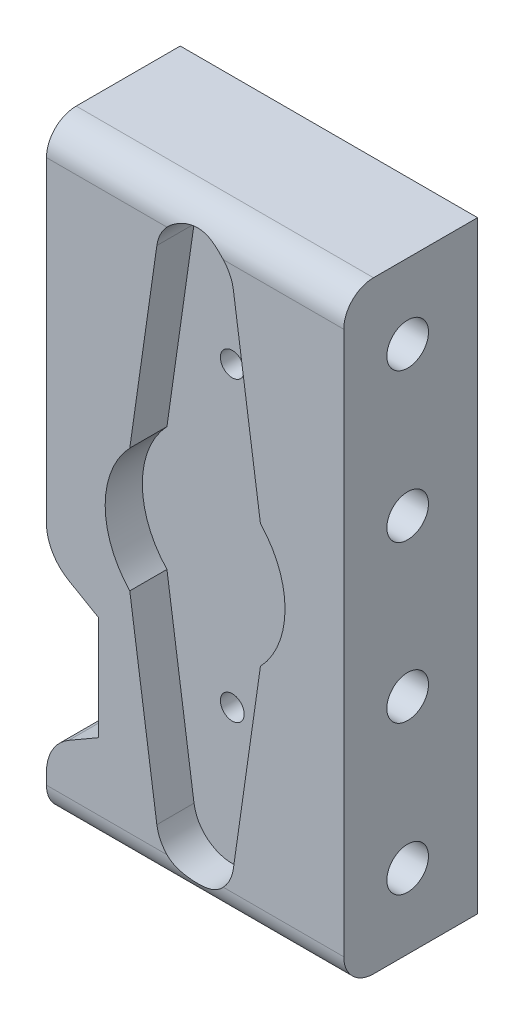
SolidWorks part; units mm, degrees
material "PLA_Holder_Servo"
ref_plane "Front Plane" through (0, 0, 0) normal (0, 0, 1) x (1, 0, 0)
ref_plane "Top Plane" through (0, 0, 0) normal (0, 1, 0) x (1, 0, 0)
ref_plane "Right Plane" through (0, 0, 0) normal (1, 0, 0) x (0, 0, -1)
sketch "Sketch1" plane through (0, 0, 0) normal (0, 0, 1) x (1, 0, 0)
  line L0 (-10, 20.2804) -> (-10, -20.2804)
  line L1 (-10, -20.2804) -> (10, -20.2804)
  line L2 (10, -20.2804) -> (10, 20.2804)
  line L3 (10, 20.2804) -> (-10, 20.2804)
  line L4 (10, -20.2804) -> (-10, 20.2804) construction
  line L5 (10, 20.2804) -> (-10, -20.2804) construction
  point P4 (0, 0)
  dimension "D1" = 20
  dimension "D2" = 40.5608
extrude "Boss-Extrude1" add sketch "Sketch1" against normal blind 9
sketch "Sketch6" plane through (10, 0, 0) normal (1, 0, 0) x (0, 0, -1)
  line L0 (0, -20.2804) -> (0, 20.2804) construction
  line L2 (4.3, 4.95) -> (4.3, 15.6283) construction
  line L3 (0, 0) -> (9, 0) construction
  line L4 (9, -20.2804) -> (9, 20.2804) construction
  line L5 (4.3, -15.2652) -> (4.3, -5.2652) construction
  line L6 (-4.0611, -10.2652) -> (12.6611, -10.2652) construction
  line L7 (9, -20.2804) -> (0, -20.2804) construction
  line L8 (-4.0611, -0.25) -> (12.6611, -0.25) construction
  circle A0 centre (4.3, -15.2652) radius 1.4
  circle A1 centre (4.3, -5.2652) radius 1.4
  circle A2 centre (4.3, 15.2652) radius 1.4
  circle A3 centre (4.3, 5.2652) radius 1.4
  point P18 (4.3, -10.2652)
  point P22 (4.3, -10.2652)
  dimension "D1" = 2.8
  dimension "D2" = 4.7
  dimension "D3" = 10.0152
  dimension "D4" = 10
  dimension "D5" = 10.0152
extrude "Cut-Extrude1" cut sketch "Sketch6" against normal blind 10
sketch "Sketch8" plane through (0, 0, 0) normal (0, 0, 1) x (1, 0, 0)
  line L0 (-10, 20.2804) -> (10, -20.2804) construction
  line L1 (-4.3945, -4.1583) -> (-2.5737, -16.8687)
  line L2 (4.3, 4.1125) -> (4.3, -4.1125) construction
  line L3 (0, -16.5) -> (0, 16.5) construction
  line L4 (2.5737, -16.8687) -> (4.3945, -4.1583)
  line L5 (-4.3, 4.1125) -> (4.3, 4.1125) construction
  line L6 (-4.3, -4.1125) -> (4.3, -4.1125) construction
  line L7 (4.3945, 4.1583) -> (2.5737, 16.8687)
  line L8 (-2.5737, 16.8687) -> (-4.3945, 4.1583)
  line L12 (-4.3, -4.1125) -> (-2.4747, -16.8545) construction
  line L13 (2.4747, -16.8545) -> (4.3, -4.1125) construction
  line L14 (4.3, 4.1125) -> (2.4747, 16.8545) construction
  line L15 (-2.4747, 16.8545) -> (-4.3, 4.1125) construction
  arc A0 (-2.5737, -16.8687) -> (2.5737, -16.8687) centre (0, -16.5) ccw
  arc A1 (4.3945, -4.1583) -> (4.3945, 4.1583) centre (0, 0) ccw
  arc A2 (2.5737, 16.8687) -> (-2.5737, 16.8687) centre (0, 16.5) ccw
  arc A3 (-4.3945, 4.1583) -> (-4.3945, -4.1583) centre (0, 0) ccw
  arc A12 (-4.3, 4.1125) -> (-4.3, -4.1125) centre (0, 0) ccw construction
  arc A13 (-2.4747, -16.8545) -> (2.4747, -16.8545) centre (0, -16.5) ccw construction
  arc A14 (4.3, -4.1125) -> (4.3, 4.1125) centre (0, 0) ccw construction
  arc A15 (2.4747, 16.8545) -> (-2.4747, 16.8545) centre (0, 16.5) ccw construction
  point P10 (0, 0)
  dimension "D1" = 5.95
  dimension "D3" = 2.5
  dimension "D2" = 8.6
  dimension "D4" = 33
  dimension "D5" = 8.225
  dimension "D6" = 0.1
extrude "Cut-Extrude2" cut sketch "Sketch8" against normal blind 2.5
fillet "Fillet1" radius 2 2 edges at (0, -20.2804, 0) (0, 20.2804, 0) tangent propagation no
sketch "Sketch9" plane through (0, 0, -2.5) normal (0, 0, 1) x (1, 0, 0)
  line L0 (0, 20) -> (0, -49980) construction
  line L1 (-6.05, 0) -> (6.05, 0) construction
  circle A0 centre (0, 10) radius 0.8
  arc A2 (-4.3945, 4.1583) -> (-4.3945, -4.1583) centre (0, 0) ccw construction
  arc A3 (4.3945, -4.1583) -> (4.3945, 4.1583) centre (0, 0) ccw construction
  circle A4 centre (0, -10) radius 0.8
  dimension "D1" = 1.6
  dimension "D2" = 10
extrude "Cut-Extrude3" cut sketch "Sketch9" against normal up to surface (6.5 mm away) up to face at (0, 0, -9)
sketch "Sketch10" plane through (-10, 0, 0) normal (-1, 0, 0) x (0, 0, 1)
  line L0 (0, -10.2652) -> (-9, -10.2652) construction
  line L1 (0, 18.2804) -> (0, -18.2804) construction
  line L2 (-9, 20.2804) -> (-9, -20.2804) construction
  line L3 (-9, -20.2804) -> (-2, -20.2804) construction
  line L4 (0, -6.7652) -> (-9, -6.7652)
  line L5 (0, -13.7652) -> (-9, -13.7652)
  line L6 (0, -13.7652) -> (0, -6.7652)
  line L7 (-9, -6.7652) -> (-9, -13.7652)
  dimension "D1" = 10.0152
  dimension "D2" = 3.5
  dimension "D3" = 3.5
extrude "Cut-Extrude4" cut sketch "Sketch10" against normal blind 3.5
chamfer "Chamfer1" distance 3.5 angle 30 2 edges at (-10, -6.7652, -4.5) (-10, -13.7652, -4.5) first distance on face at (-8.25, -6.7652, -4.5) first distance on face at (-8.25, -13.7652, -4.5)
fillet "Fillet2" radius 3 2 edges at (-10, -4.7444, -4.5) (-10, -15.7859, -4.5)
